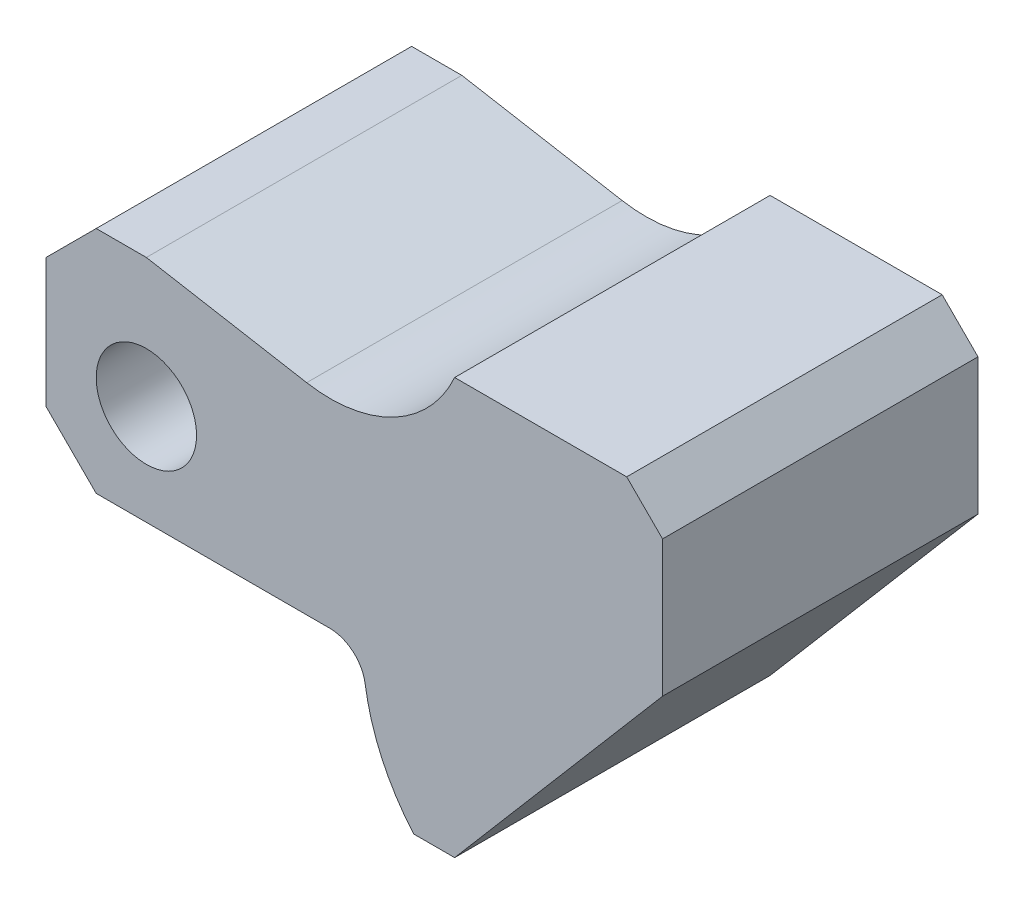
SolidWorks part; units mm, degrees
material "AISI 1020"
ref_plane "Front Plane" through (0, 0, 0) normal (0, 0, 1) x (1, 0, 0)
ref_plane "Top Plane" through (0, 0, 0) normal (0, 1, 0) x (1, 0, 0)
ref_plane "Right Plane" through (0, 0, 0) normal (1, 0, 0) x (0, 0, -1)
sketch "Sketch4" plane through (0, 0, 0) normal (0, 0, 1) x (1, 0, 0)
  line L0 (-153.4752, 21.7594) -> (-153.4752, 53.7594)
  line L1 (-153.4752, 53.7594) -> (-139.4752, 53.7594)
  line L2 (-139.4752, 53.7594) -> (-117.1138, 49.8164)
  line L3 (-96.4752, 60.7594) -> (-67.4752, 60.7594)
  line L4 (-67.4752, 60.7594) -> (-67.4752, 36.7594)
  line L5 (-67.4752, 36.7594) -> (-96.4752, 2.7594)
  line L6 (-96.4752, 2.7594) -> (-102.1782, 2.7594)
  line L7 (-153.4752, 21.7594) -> (-113.8997, 21.7594)
  arc A0 (-117.1138, 49.8164) -> (-96.4752, 60.7594) centre (-113.8145, 68.5278) ccw
  arc A1 (-102.1782, 2.7594) -> (-108.954, 17.4947) centre (-80.2693, 21.7594) cw construction
  arc A2 (-108.954, 17.4947) -> (-113.8997, 21.7594) centre (-113.8997, 16.7594) ccw construction
  arc A3 (-113.8997, 21.7594) -> (-108.954, 17.4947) centre (-113.8997, 16.7594) cw
  arc A4 (-108.954, 17.4947) -> (-102.1782, 2.7594) centre (-80.2693, 21.7594) ccw
  dimension "D4" = 19
  dimension "D9" = 29
  dimension "D10" = 5
  dimension "D1" = 32
  dimension "D2" = 14
  dimension "D3" = 10
  dimension "D5" = 29
  dimension "D6" = 24
  dimension "D7" = 29
  dimension "D8" = 58
  dimension "D11" = 19
  dimension "D12" = 86
  dimension "D13" = 19
extrude "Boss-Extrude1" add sketch "Sketch4" along normal blind 44
sketch "Sketch5" plane through (0, 0, 0) normal (0, 0, 1) x (1, 0, 0)
  line L0 (-153.4752, 53.7594) -> (-153.4752, 21.7594) construction
  line L1 (-153.4752, 21.7594) -> (-113.8997, 21.7594) construction
  circle A0 centre (-139.4752, 35.7594) radius 7
  dimension "D1" = 14
  dimension "D2" = 14
extrude "Cut-Extrude1" cut sketch "Sketch5" along normal through all
chamfer "Chamfer1" distance 7 angle 45 1 edges at (-153.4752, 53.7594, 22)
chamfer "Chamfer2" distance 7 angle 45 1 edges at (-153.4752, 21.7594, 22)
chamfer "Chamfer3" distance 5 angle 45 1 edges at (-67.4752, 60.7594, 22)
sketch "Sketch8" plane through (0, 0, 44) normal (0, 0, 1) x (1, 0, 0)
  line L0 (-67.4752, 36.7594) -> (-67.4752, 55.7594) construction
  line L1 (-72.4752, 60.7594) -> (-96.4752, 60.7594) construction
  circle A0 centre (-81.4752, 46.7594) radius 6.1286
  dimension "D1" = 14
  dimension "D2" = 14
extrude "Cut-Extrude2" [suppressed] cut sketch "Sketch8" against normal through all
sketch "Sketch9" plane through (0, 53.7594, 0) normal (0, 1, 0) x (1, 0, 0)
  line L1 (-153.4752, -44) -> (-119.4752, -44)
  line L2 (-153.4752, -44) -> (-153.4752, -25)
  line L3 (-153.4752, -25) -> (-119.4752, -25)
  line L4 (-119.4752, -44) -> (-119.4752, -25)
  dimension "D1" = 19
  dimension "D2" = 52
extrude "Cut-Extrude3" [suppressed] cut sketch "Sketch9" against normal through all
sketch "Sketch10" plane through (0, 0, 0) normal (0, 0, -1) x (-1, 0, 0)
  line L0 (96.4752, 2.7594) -> (67.4752, 36.7594) construction
  line L1 (67.4752, 36.7594) -> (67.4752, 55.7594) construction
  line L2 (72.4752, 60.7594) -> (96.4752, 60.7594) construction
  line L3 (77.7105, 24.7594) -> (67.4752, 36.7594)
  line L4 (67.4752, 36.7594) -> (67.4752, 55.7594)
  line L5 (67.4752, 55.7594) -> (72.4752, 60.7594)
  line L6 (72.4752, 60.7594) -> (96.4752, 60.7594)
  arc A0 (106.2383, 51.1037) -> (77.7105, 24.7594) centre (67.4752, 64.4612) cw
  arc A1 (96.4752, 60.7594) -> (117.1138, 49.8164) centre (113.8145, 68.5278) ccw construction
  arc A2 (96.4752, 60.7594) -> (106.2383, 51.1037) centre (113.8145, 68.5278) ccw
  dimension "D1" = 41
  dimension "D2" = 36
extrude "Cut-Extrude4" [suppressed] cut sketch "Sketch10" against normal blind 24 from offset 12 offset against normal yes
